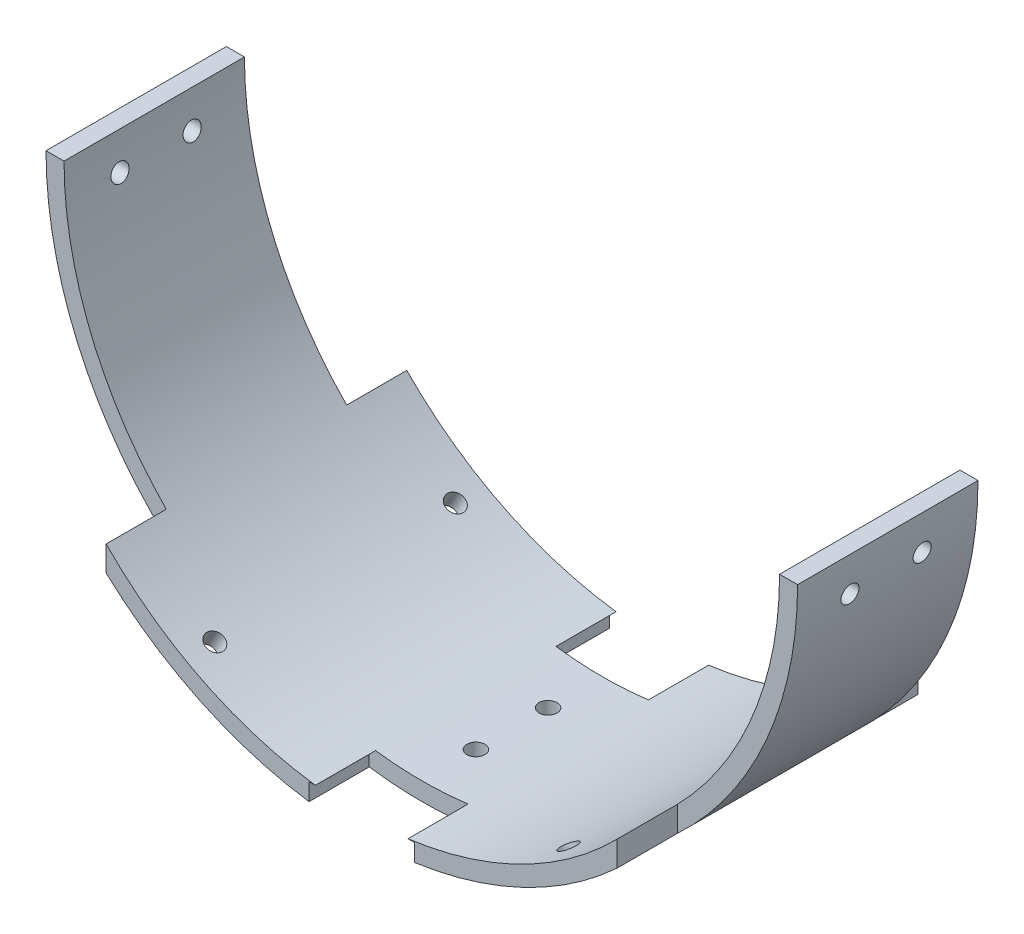
SolidWorks part; units mm, degrees
ref_plane "Front Plane" through (0, 0, 0) normal (0, 0, 1) x (1, 0, 0)
ref_plane "Top Plane" through (0, 0, 0) normal (0, 1, 0) x (1, 0, 0)
ref_plane "Right Plane" through (0, 0, 0) normal (1, 0, 0) x (0, 0, -1)
sketch "Sketch1" plane through (0, 0, 0) normal (0, 0, 1) x (1, 0, 0)
  line L1 (-59.5, 0) -> (-62.5, 0)
  line L2 (59.5, 0) -> (62.5, 0)
  circle A0 centre (0, 0) radius 62.5
  circle A1 centre (0, 0) radius 59.5
  dimension "D1" = 125
  dimension "D2" = 119
extrude "Boss-Extrude1" add sketch "Sketch1" along normal blind 50 contours A1 L1 A0 L2 region at (0, -60.8975, 0)
ref_plane "Plane1" through (-59.5, 0, 0) normal (1, 0, 0) x (0, 0, -1)
sketch "Sketch3" plane through (0, 0, 0) normal (0, 1, 0) x (1, 0, 0)
  line L1 (-62.5, -50) -> (-42.5, -50)
  line L2 (-62.5, -50) -> (-62.5, -40)
  line L3 (-62.5, -40) -> (-42.5, -40)
  line L4 (-42.5, -50) -> (-42.5, -40)
  line L5 (62.5, -50) -> (42.5, -50)
  line L6 (62.5, -50) -> (62.5, -40)
  line L7 (62.5, -40) -> (42.5, -40)
  line L8 (42.5, -50) -> (42.5, -40)
  dimension "D1" = 10
  dimension "D2" = 20
  dimension "D3" = 10
  dimension "D4" = 20
extrude "Cut-Extrude2" cut sketch "Sketch3" against normal through all both
sketch "Sketch4" plane through (0, 0, 50) normal (0, 0, 1) x (1, 0, 0)
  line L1 (-8.75, -66) -> (8.75, -66)
  line L2 (-8.75, -66) -> (-8.75, -59)
  line L3 (-8.75, -59) -> (8.75, -59)
  line L4 (8.75, -66) -> (8.75, -59)
  line L5 (-8.75, -66) -> (8.75, -59) construction
  line L6 (-8.75, -59) -> (8.75, -66) construction
  arc A0 (-42.5, -45.8258) -> (42.5, -45.8258) centre (0, 0) ccw construction
  point P0 (0, -62.5)
  dimension "D1" = 17.5
  dimension "D2" = 7
extrude "Cut-Extrude3" cut sketch "Sketch4" against normal blind 10
sketch "Sketch9" plane through (0, 0, 0) normal (0, 0, 1) x (1, 0, 0)
  line L0 (-56.6442, -26.4136) -> (-52.1127, -24.3006)
  line L1 (-48.5716, -39.3325) -> (-44.6859, -36.1859)
  line L2 (-7.6168, -62.0341) -> (-7.0075, -57.0714)
  line L3 (7.6168, -62.0341) -> (7.0075, -57.0714)
  line L4 (48.5716, -39.3325) -> (44.6859, -36.1859)
  line L5 (56.6442, -26.4136) -> (52.1127, -24.3006)
  circle A0 centre (0, 0) radius 57.5
  circle A1 centre (0, 0) radius 62.5
  circle A2 centre (0, 0) radius 61
  dimension "D1" = 5
  dimension "D2" = 115
  dimension "D3" = 122
extrude "Boss-Extrude2" add sketch "Sketch9" along normal blind 10 contours L0 A1 L1 A0 | L2 A1 L3 A0 | L4 A1 L5 A0 region at (-50.1365, -31.3288, 0) region at (50.1365, -31.3288, 0) region at (0, -59.1199, 0)
ref_plane "Plane2" through (0, 0, 0) normal (0.8746, -0.4848, 0) x (0, 0, -1)
ref_plane "Plane6" through (-28.8462, -52.0399, 0) normal (0.4848, 0.8746, 0) x (0.8746, -0.4848, 0)
ref_plane "Plane7" through (0, 0, 0) normal (0.8746, 0.4848, 0) x (0, 0, -1)
ref_plane "Plane8" through (28.8462, -52.0399, 0) normal (-0.4848, 0.8746, 0) x (0.8746, 0.4848, 0)
sketch "Sketch15" plane through (0, 0, 0) normal (0, 0, 1) x (1, 0, 0)
  line L0 (-56.6442, -26.4136) -> (-52.1127, -24.3006)
  line L1 (-48.5716, -39.3325) -> (-44.6859, -36.1859)
  line L2 (-7.6168, -62.0341) -> (-7.0075, -57.0714)
  line L3 (7.6168, -62.0341) -> (7.0075, -57.0714)
  line L4 (48.5716, -39.3325) -> (44.6859, -36.1859)
  line L5 (56.6442, -26.4136) -> (52.1127, -24.3006)
  circle A0 centre (0, 0) radius 57.5
  circle A1 centre (0, 0) radius 62.5
  circle A2 centre (0, 0) radius 61
  dimension "D1" = 5
  dimension "D2" = 115
  dimension "D3" = 122
extrude "Cut-Extrude6" cut sketch "Sketch15" along normal blind 10 contours L0 A2 L1 A0 | L2 A2 L3 A0 | L4 A2 L5 A0 region at (-50.1365, -31.3288, 0) region at (50.1365, -31.3288, 0) region at (0, -59.1199, 0)
sketch "Sketch16" plane through (-28.8462, -52.0399, 0) normal (0.4848, 0.8746, 0) x (0.8746, -0.4848, 0)
  line L0 (-68.75, 0) -> (68.75, 0) construction
  line L3 (-54.6637, -40) -> (-54.6637, 0) construction
  circle A0 centre (-0.6637, -45) radius 1.5
  dimension "D1" = 45
  dimension "D2" = 3
  dimension "D3" = 54
extrude "Cut-Extrude7" cut sketch "Sketch16" against normal blind 10 and the other way blind 10
sketch "Sketch17" plane through (28.8462, -52.0399, 0) normal (-0.4848, 0.8746, 0) x (0.8746, 0.4848, 0)
  line L0 (-52.0399, 0) -> (-59.3551, 0) construction
  line L1 (54.6637, -40) -> (54.6637, 0) construction
  circle A0 centre (0.6637, -45) radius 1.5
  dimension "D1" = 3
  dimension "D2" = 45
  dimension "D3" = 54
extrude "Cut-Extrude8" cut sketch "Sketch17" against normal blind 10 and the other way blind 10
ref_plane "Plane10" through (59.5, 0, 0) normal (-1, 0, 0) x (0, 1, 0)
sketch "Sketch18" plane through (59.5, 0, 0) normal (-1, 0, 0) x (0, 1, 0)
  line L1 (0, -40) -> (0, 0) construction
  line L2 (0, 0) -> (-62.5, 0) construction
  circle A0 centre (-6, -31) radius 1.5
  dimension "D1" = 3
  dimension "D2" = 31
  dimension "D3" = 6
extrude "Cut-Extrude9" cut sketch "Sketch18" against normal blind 10 and the other way blind 127
ref_plane "Plane11" through (0, -59.5, 0) normal (0, 1, 0) x (1, 0, 0)
sketch "Sketch19" plane through (0, -59.5, 0) normal (0, 1, 0) x (1, 0, 0)
  line L0 (-62.5, -40) -> (-62.5, 0) construction
  line L1 (-53.9253, 0) -> (-59.5, 0) construction
  circle A0 centre (0, -31) radius 1.5
  dimension "D1" = 3
  dimension "D3" = 31
  dimension "D2" = 62.5
extrude "Cut-Extrude10" cut sketch "Sketch19" against normal blind 10 and the other way blind 10
ref_plane "Plane12" through (0, 0, 25) normal (0, 0, 1) x (1, 0, 0)
mirror "Mirror4" about plane through (0, 0, 25) normal (0, 0, 1) of "Cut-Extrude10", "Cut-Extrude9", "Cut-Extrude8", "Cut-Extrude7", "Cut-Extrude6", "Boss-Extrude2", "Cut-Extrude3", "Cut-Extrude2"
